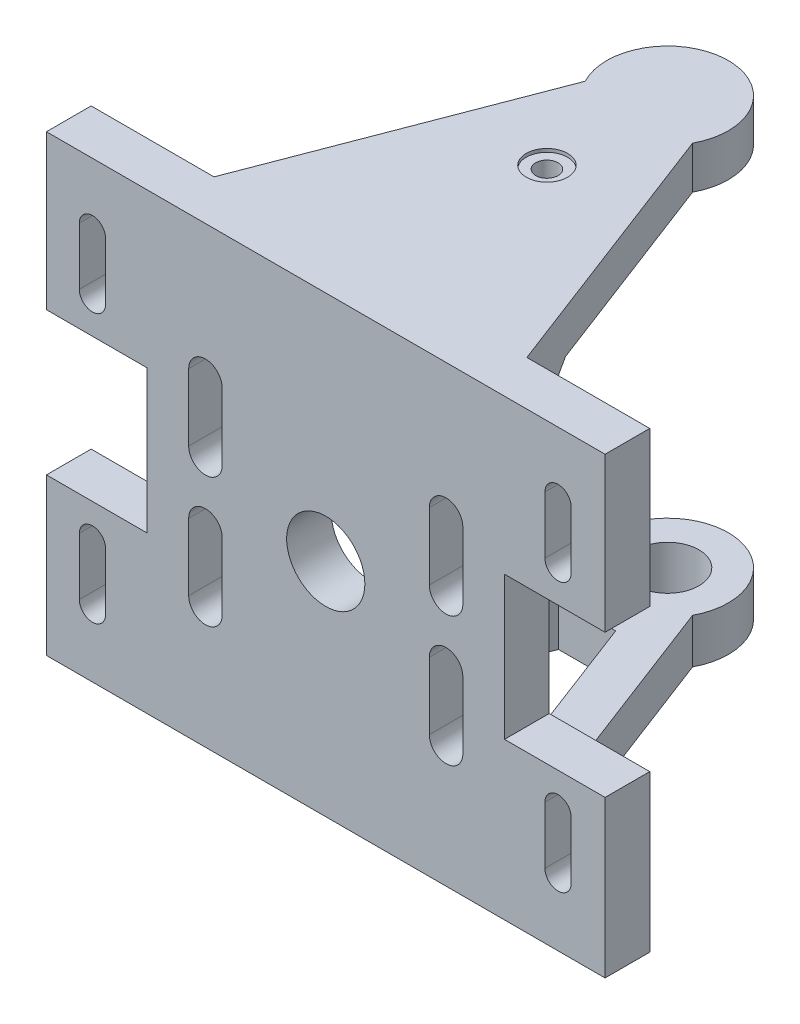
SolidWorks part; units mm, degrees
note: The reader was unsure of these and kept them because the rebuilt part matched: shared geometry of "Esboço1<2>".
ref_plane "Plano frontal" through (0, 0, 0) normal (0, 0, 1) x (1, 0, 0)
ref_plane "Plano superior" through (0, 0, 0) normal (0, 1, 0) x (1, 0, 0)
ref_plane "Plano direito" through (0, 0, 0) normal (1, 0, 0) x (0, 0, -1)
sketch "Esboço1" plane through (0, 0, 0) normal (0, 0, 1) x (1, 0, 0)
  line L0 (-84.9189, -29.1762) -> (-75.9189, -29.1762)
  line L1 (-84.9189, -15.3762) -> (-34.9189, -15.3762)
  line L2 (-84.9189, -15.3762) -> (-84.9189, -29.1762)
  line L3 (-84.9189, -55.9762) -> (-34.9189, -55.9762)
  line L4 (-34.9189, -15.3762) -> (-34.9189, -29.1762)
  line L5 (-75.9189, -29.1762) -> (-75.9189, -41.9762)
  line L6 (-75.9189, -41.9762) -> (-84.9189, -41.9762)
  line L7 (-84.9189, -41.9762) -> (-84.9189, -55.9762)
  line L8 (-70.6882, -27.3762) -> (-70.6882, -33.3762) construction
  line L9 (-80.8025, -20.9895) -> (-80.8025, -26.1183) construction
  line L10 (-79.6286, -20.9895) -> (-79.6286, -26.1183)
  line L11 (-81.9764, -20.9895) -> (-81.9764, -26.1183)
  line L12 (-69.1882, -27.3762) -> (-69.1882, -33.3762)
  line L13 (-80.8025, -50.1669) -> (-80.8025, -45.038) construction
  line L14 (-79.6286, -50.1669) -> (-79.6286, -45.038)
  line L15 (-81.9764, -50.1669) -> (-81.9764, -45.038)
  line L16 (-39.1274, -20.9895) -> (-39.1274, -26.1183) construction
  line L17 (-40.3013, -20.9895) -> (-40.3013, -26.1183)
  line L18 (-37.9535, -20.9895) -> (-37.9535, -26.1183)
  line L19 (-39.1274, -50.1669) -> (-39.1274, -45.038) construction
  line L20 (-40.3013, -50.1669) -> (-40.3013, -45.038)
  line L21 (-37.9535, -50.1669) -> (-37.9535, -45.038)
  line L22 (-43.9189, -41.9762) -> (-34.9189, -41.9762)
  line L23 (-43.9189, -29.1762) -> (-43.9189, -41.9762)
  line L24 (-34.9189, -29.1762) -> (-43.9189, -29.1762)
  line L25 (-34.9189, -41.9762) -> (-34.9189, -55.9762)
  line L26 (-72.1882, -27.3762) -> (-72.1882, -33.3762)
  line L29 (-70.6882, -44.9762) -> (-70.6882, -38.9762) construction
  line L30 (-69.1882, -44.9762) -> (-69.1882, -38.9762)
  line L31 (-72.1882, -44.9762) -> (-72.1882, -38.9762)
  line L32 (-49.1496, -44.9762) -> (-49.1496, -38.9762) construction
  line L33 (-50.6496, -44.9762) -> (-50.6496, -38.9762)
  line L34 (-47.6496, -44.9762) -> (-47.6496, -38.9762)
  line L35 (-49.1496, -27.3762) -> (-49.1496, -33.3762) construction
  line L36 (-50.6496, -27.3762) -> (-50.6496, -33.3762)
  line L37 (-47.6496, -27.3762) -> (-47.6496, -33.3762)
  arc A0 (-79.6286, -20.9895) -> (-81.9764, -20.9895) centre (-80.8025, -20.9895) ccw
  arc A1 (-81.9764, -26.1183) -> (-79.6286, -26.1183) centre (-80.8025, -26.1183) ccw
  arc A2 (-79.6286, -50.1669) -> (-81.9764, -50.1669) centre (-80.8025, -50.1669) cw
  arc A3 (-81.9764, -45.038) -> (-79.6286, -45.038) centre (-80.8025, -45.038) cw
  arc A4 (-40.3013, -20.9895) -> (-37.9535, -20.9895) centre (-39.1274, -20.9895) cw
  arc A5 (-37.9535, -26.1183) -> (-40.3013, -26.1183) centre (-39.1274, -26.1183) cw
  arc A6 (-40.3013, -50.1669) -> (-37.9535, -50.1669) centre (-39.1274, -50.1669) ccw
  arc A7 (-37.9535, -45.038) -> (-40.3013, -45.038) centre (-39.1274, -45.038) ccw
  arc A8 (-69.1882, -44.9762) -> (-72.1882, -44.9762) centre (-70.6882, -44.9762) cw
  circle A9 centre (-59.9189, -36.1762) radius 3.5
  arc A10 (-72.1882, -38.9762) -> (-69.1882, -38.9762) centre (-70.6882, -38.9762) cw
  arc A11 (-50.6496, -44.9762) -> (-47.6496, -44.9762) centre (-49.1496, -44.9762) ccw
  arc A12 (-47.6496, -38.9762) -> (-50.6496, -38.9762) centre (-49.1496, -38.9762) ccw
  arc A13 (-69.1882, -27.3762) -> (-72.1882, -27.3762) centre (-70.6882, -27.3762) ccw
  arc A14 (-72.1882, -33.3762) -> (-69.1882, -33.3762) centre (-70.6882, -33.3762) ccw
  arc A15 (-50.6496, -27.3762) -> (-47.6496, -27.3762) centre (-49.1496, -27.3762) cw
  arc A16 (-47.6496, -33.3762) -> (-50.6496, -33.3762) centre (-49.1496, -33.3762) cw
  point P12 (-80.8025, -23.5539)
  point P17 (-70.6882, -30.3762)
  point P21 (-80.8025, -47.6024)
  point P28 (-39.1274, -23.5539)
  point P35 (-39.1274, -47.6024)
  point P52 (-70.6882, -41.9762)
  point P62 (-49.1496, -41.9762)
  point P69 (-49.1496, -30.3762)
  dimension "D6" = 6
  dimension "D7" = 7
  dimension "D8" = 13.8
  dimension "D10" = 1.1739
  dimension "D1" = 13.8
  dimension "D2" = 40.6
  dimension "D3" = 50
  dimension "D4" = 12.8
  dimension "D5" = 9
  dimension "D9" = 12.8
  dimension "D11" = 3
  dimension "D12" = 3.0618
  dimension "D13" = 3.0618
extrude "Ressalto-extrusão3" add sketch "Esboço1" along normal blind 2
sketch "Esboço3" plane through (0, -55.9762, 0) normal (0, -1, 0) x (1, 0, 0)
  line L0 (-84.9189, 0) -> (-34.9189, 0) construction
  line L1 (-69.9189, 0) -> (-49.9189, 0)
  line L4 (-73.9189, 0) -> (-66.7668, -18.6825)
  line L5 (-45.9189, 0) -> (-53.0689, -18.6825)
  line L6 (-66.7668, -8.2039) -> (-64.4189, -14.3148)
  line L7 (-64.4189, -14.3148) -> (-62.4722, -19.3815)
  line L8 (-55.4189, -14.3148) -> (-53.0892, -8.2039)
  line L9 (-66.7668, -8.2039) -> (-53.0892, -8.2039)
  line L10 (-73.9189, 0) -> (-69.9189, 0)
  line L11 (-49.9189, 0) -> (-45.9189, 0)
  line L12 (-66.7668, -18.6825) -> (-64.719, -24.0319)
  line L13 (-53.0689, -18.6825) -> (-55.1162, -24.0319)
  line L14 (-55.4189, -14.3148) -> (-57.3505, -19.3815)
  line L15 (-57.3505, -19.3815) -> (-62.4722, -19.3815)
  arc A0 (-64.719, -24.0319) -> (-55.1162, -24.0319) centre (-59.9176, -26.5951) ccw
  circle A1 centre (-59.9176, -26.5951) radius 2.8
  point P0 (-69.9189, 0)
  point P1 (-49.9189, 0)
  point P8 (-73.9189, 0)
  point P11 (-45.9189, 0)
  dimension "D5" = 4
  dimension "D6" = 4
  dimension "D3" = 5.6
  dimension "D1" = 15
  dimension "D2" = 15
  dimension "D9" = 7.1521
  dimension "D10" = 7.15
extrude "Ressalto-extrusão4" add sketch "Esboço3" against normal blind 4
sketch "Esboço4" plane through (0, -15.3762, 0) normal (0, 1, 0) x (1, 0, 0)
  line L0 (-73.9189, 0) -> (-64.719, 24.0319)
  line L1 (-45.9189, 0) -> (-55.1162, 24.0319)
  line L2 (-73.9189, 0) -> (-69.9189, 0)
  line L3 (-69.9189, 0) -> (-49.9189, 0)
  line L6 (-49.9189, 0) -> (-45.9189, 0)
  arc A0 (-64.719, 24.0319) -> (-55.1162, 24.0319) centre (-59.9176, 26.5951) cw
extrude "Ressalto-extrusão6" add sketch "Esboço4" against normal blind 3.8
sketch "Esboço5" plane through (0, -19.1762, 0) normal (0, -1, 0) x (1, 0, 0)
  line L0 (-62.4176, -11.6451) -> (-64.0676, -26.5951)
  line L1 (-57.4176, -11.6451) -> (-55.7676, -26.5951)
  arc A0 (-64.0676, -26.5951) -> (-55.7676, -26.5951) centre (-59.9176, -26.5951) ccw
  arc A1 (-57.4176, -11.6451) -> (-62.4176, -11.6451) centre (-59.9176, -11.6451) ccw
  point P1 (-59.9176, -30.7451)
  point P2 (-59.9176, -15.7951)
  point P9 (-59.9176, -9.1451)
  dimension "D1" = 21.6
  dimension "D3" = 5
  dimension "D2" = 4.15
  dimension "D4" = 0
  dimension "D5" = 10.8
extrude "Ressalto-extrusão7" add sketch "Esboço1<2>" along normal blind 4
sketch "Esboço1<2>" plane through (0, 0, 0) normal (0, 0, 1) x (1, 0, 0) same geometry as "Esboço1"
extrude "Corte-extrusão1" cut sketch "Esboço5" against normal blind 1.8
sketch "Esboço12" plane through (0, -17.3762, 0) normal (0, -1, 0) x (1, 0, 0)
  circle A0 centre (-59.9176, -15.7951) radius 1
  point P0 (-59.9176, -26.5951)
  point P1 (-59.9176, -15.7951)
  dimension "D2" = 2
  dimension "D1" = 10.8
extrude "Corte-extrusão2" cut sketch "Esboço12" against normal through all
hole_wizard "Rebaixo para parafuso com cabeça panela de M1.62" positions "Esboço17" profile "Esboço16" counterbore size "M1.6" standard "ISO" end condition through all
sketch "Esboço17" plane through (0, -15.3762, 0) normal (0, 1, 0) x (1, 0, 0)
  point P0 (-59.9176, 15.7951)
  point P3 (-59.9176, 15.7951)
  point P5 (-59.9176, 15.7951)
  point P7 (-59.9176, 15.7951)
sketch "Esboço16" plane through (-59.9176, -15.3762, -15.7951) normal (1, 0, 0) x (0, 0, 1)
  line L0 (0, 0) -> (0, 40.6)
  line L1 (0, 40.6) -> (1, 40.6)
  line L3 (1, 40.6) -> (1, 0.3)
  line L4 (1, 0.3) -> (1.85, 0.3)
  line L5 (1.85, 0.3) -> (1.85, 0)
  line L7 (1.85, 0) -> (0, 0)
  line L11 (0, -6.35) -> (0, 107.95) construction
  dimension "Thru Hole Dia." = 2
  dimension "Thru Hole Depth" = 40.6
  dimension "C'Bore Dia." = 3.7
  dimension "C'Bore Depth" = 0.3
sketch "Esboço19" plane through (-40.0525, 0, 15.3285) normal (0.9339, 0, -0.3574) x (-0.3574, 0, -0.9339)
  line L0 (22.4127, -19.1762) -> (16.4127, -23.1762)
  line L1 (16.4127, -19.1762) -> (42.1444, -19.1762) construction
  line L2 (16.4127, -23.1762) -> (16.4127, -19.1762)
  line L3 (16.4127, -19.1762) -> (22.4127, -19.1762)
  dimension "D1" = 4
  dimension "D2" = 6
sketch "Esboço21" plane through (-64.4706, 0, -24.6807) normal (-0.9339, 0, -0.3575) x (-0.3575, 0, 0.9339)
  line L0 (20.4274, -19.1762) -> (26.4274, -23.1762)
  line L1 (0.6947, -19.1762) -> (26.4274, -19.1762) construction
  line L2 (26.4274, -23.1762) -> (26.4274, -19.1762)
  line L3 (26.4274, -19.1762) -> (20.4274, -19.1762)
  dimension "D1" = 6
  dimension "D2" = 4
loft "Loft1" add profiles "Esboço19", "Esboço21"
sketch "Esboço24" plane through (-64.4706, 0, -24.6807) normal (-0.9339, 0, -0.3575) x (-0.3575, 0, 0.9339)
  line L0 (26.4274, -51.9762) -> (26.4274, -47.9762)
  line L1 (26.4274, -51.9762) -> (20.4274, -51.9762)
  line L2 (26.4274, -51.9762) -> (0.6947, -51.9762) construction
  line L3 (20.4274, -51.9762) -> (26.4274, -47.9762)
  line L4 (26.4274, -47.9762) -> (26.4152, -47.9759)
  dimension "D1" = 6
  dimension "D2" = 4
sketch "Esboço25" plane through (-40.0525, 0, 15.3285) normal (0.9339, 0, -0.3574) x (-0.3574, 0, -0.9339)
  line L0 (16.4127, -51.9762) -> (16.4127, -47.9762)
  line L1 (16.4127, -47.9762) -> (22.4127, -51.9762)
  line L2 (42.1444, -51.9762) -> (16.4127, -51.9762) construction
  line L3 (22.4127, -51.9762) -> (16.4127, -51.9762)
  dimension "D1" = 4
  dimension "D2" = 6
loft "Loft2" add profiles "Esboço25" section "Esboço25" section "Esboço24"
